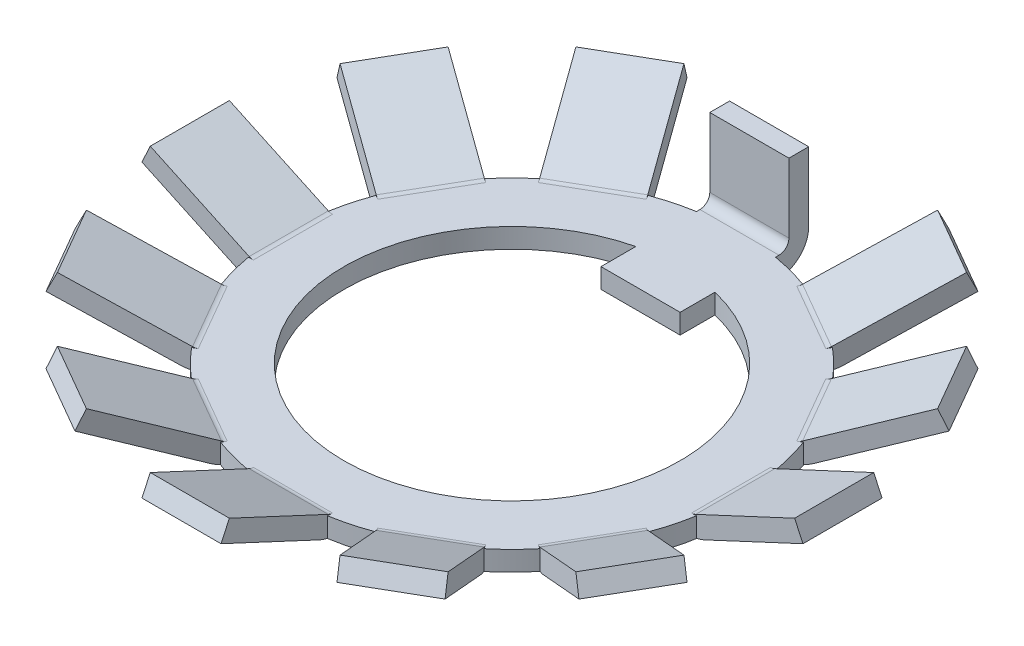
SolidWorks part; units mm, degrees
note: '?' marks a value the reader was unsure of.
revolve "Base" add sketch "Esquisse1" angle 360 about L10
sketch "Esquisse1" plane through (0, 0, 0) normal (0, 0, 1) x (1, 0, 0)
  line L0 (0, -0.0105) -> (0, -4.0105) construction
  line L1 (8.5, 0) -> (11.5, 0)
  line L2 (8.5, 0) -> (8.5, 1)
  line L3 (8.5, 1) -> (11.5, 1)
  line L4 (11.5, 0) -> (11.5, 1)
  line L5 (8.5, 0) -> (-8.5, 0) construction
  line L6 (11.5, 0) -> (-11.5, 0) construction
  line L7 (28.1031, 0) -> (0, 0) construction
  line L8 (0, 0) -> (-33, 0) construction
  line L9 (0, 0) -> (-37.363, 0) construction
  line L10 (0, 0) -> (0, 4) construction
  dimension "Sr4" = 11.5
  dimension "Epaisseur" = 1
  dimension "Diamètre nominal" = 17
  dimension "Diamètre d4" = 23
  dimension "Diamètre Extérieur d5" = 33
  dimension "Largeur lame ext f" = 4
  dimension "Largeur lame int f1" = 4
  dimension "Sr3" = 8.5
extrude "Languette pliée" add sketch "Esquisse3" along normal mid plane 4 thin thin type mid plane wall 1
sketch "Esquisse3" plane through (0, 0, 0) normal (1, 0, 0) x (0, 0, -1)
  line L0 (8.5, 0.5) -> (6.5, 0.5)
  line L2 (0, 0) -> (37, 0) construction
  line L4 (8.5, 0.5) -> (11.5, 0.5)
  line L6 (12.5, 1.5) -> (12.5, 5)
  line L13 (-8.5, 1) -> (-8.5, 0) construction
  line L14 (11.5, 1) -> (-11.5, 1) construction
  line L15 (8.5, 0) -> (8.5, 1) construction
  line L16 (11.5, 0) -> (11.5, 1) construction
  arc A0 (11.5, 0.5) -> (12.5, 1.5) centre (11.5, 1.5) ccw
  dimension "Rl2" = 1
  dimension "LLC" = 4
  dimension "Longueur M" = 15
ref_plane "Face" through (0, 0, 0) normal (0, 0, 1) x (1, 0, 0)
ref_plane "Dessus" through (0, 0, 0) normal (0, 1, 0) x (1, 0, 0)
ref_plane "Droite" through (0, 0, 0) normal (1, 0, 0) x (0, 0, -1)
ref_axis "Axe1" through (0, 5.25, 0) along (0, -1, 0)?
ref_plane "Plan Languette" through (0, 0, 0) normal (-0.866, 0, -0.5) x (-0.5, 0, 0.866)
sketch "Esquisse2" plane through (0, 0, 0) normal (-0.866, 0, -0.5) x (-0.5, 0, 0.866)
  line L0 (-8.5, 0.5) -> (-11.0774, 0.5)
  line L3 (-11.5, 0.5937) -> (-16.5, 2.9252)
  line L4 (0, 0) -> (0, 4) construction
  line L5 (-8.5, 1) -> (-8.5, 0) construction
  line L6 (-11.5, 1) -> (-11.5, 0) construction
  arc A0 (-11.0774, 0.5) -> (-11.5, 0.5937) centre (-11.0774, 1.5) cw
  point P9 (-11.2991, 0.5)
  dimension "D1" = 25
  dimension "Sd5" = 16.5
extrude "Languette" add sketch "Esquisse2" along normal mid plane 4 thin thin type mid plane wall 1
pattern_circular "Nbr de languettes" count 11 every 30 about axis through (0, 0, 0) along (0, 1, 0) of "Languette"
equation "\"Sr4@Esquisse1\" = \"Diamètre d4@Esquisse1\"/2"
equation "\"Sr3@Esquisse1\" = \"Diamètre nominal@Esquisse1\"/2"
equation "\"RL2@Esquisse2\" = \"Epaisseur@Esquisse1\""
equation "\"Sd5@Esquisse2\" = \"Diamètre Extérieur d5@Esquisse1\" /2"
equation "\"Rl2@Esquisse3\" = \"Epaisseur@Esquisse1\"  "
equation "\"LLC@Esquisse3\" =  \"Largeur lame ext f@Esquisse1\"  "
equation "\"EpL0@Languette\" =  \"Epaisseur@Esquisse1\"  "
equation "\"Sdf@Languette\" =  \"Largeur lame ext f@Esquisse1\"  "
equation "\"Df1@Languette pliée\" =  \"Largeur lame int f1@Esquisse1\"  "
equation "\"EpL1@Languette pliée\" =  \"Epaisseur@Esquisse1\"  "
equation "\"D1@Nbr de languettes\" =int( (\"Diamètre d4@Esquisse1\"*pi)/(1.5*\"Df1@Languette pliée\"))-1"
equation "\"D1@Plan Languette\" = 180+(360/int( (\"Diamètre d4@Esquisse1\"*pi)/(1.5*\"Df1@Languette pliée\")))"
equation "\"D2@Nbr de languettes\" = \"D1@Plan Languette\"-180"
